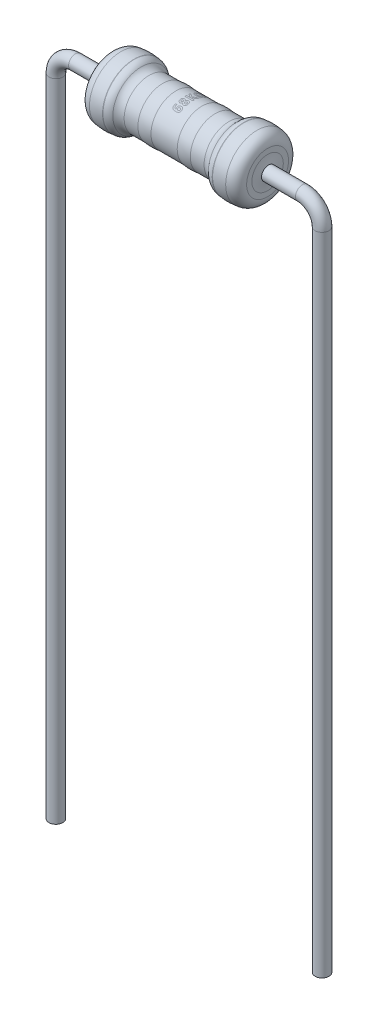
SolidWorks part; units mm, degrees
material "Plain Carbon Steel"
ref_plane "Front Plane" through (0, 0, 0) normal (0, 0, 1) x (1, 0, 0)
ref_plane "Top Plane" through (0, 0, 0) normal (0, 1, 0) x (1, 0, 0)
ref_plane "Right Plane" through (0, 0, 0) normal (1, 0, 0) x (0, 0, -1)
sketch "Sketch1" plane through (0, 0, 0) normal (0, 0, 1) x (1, 0, 0)
  line L0 (-4.33, 0) -> (4.33, 0)
  line L1 (-5.08, -0.75) -> (-5.08, -25.4)
  line L2 (5.08, -0.75) -> (5.08, -25.4)
  line L3 (-5.08, -25.4) -> (5.08, -25.4) construction
  line L4 (0, 0) -> (0, -25.4) construction
  arc A0 (-4.33, 0) -> (-5.08, -0.75) centre (-4.33, -0.75) ccw
  arc A1 (4.33, 0) -> (5.08, -0.75) centre (4.33, -0.75) cw
  dimension "D2" = 0.75
  dimension "D1" = 10.16
  dimension "D3" = 25.4
ref_plane "Plane1" through (-5.08, -25.4, 0) normal (0, -1, 0) x (-1, 0, 0)
sketch "Sketch2" plane through (-5.08, -25.4, 0) normal (0, -1, 0) x (-1, 0, 0)
  circle A0 centre (0, 0) radius 0.265
  dimension "D1" = 0.53
sweep "Sweep1" add profiles "Sketch2" path "Sketch1"
sketch "Sketch3" plane through (0, 0, 0) normal (0, 0, 1) x (1, 0, 0)
  line L0 (-3, 0) -> (3, 0)
  line L5 (-3, 0) -> (-3, 1.2)
  line L6 (3, 0) -> (3, 1.2)
  line L7 (-3, 1.2) -> (-1.75, 1.2)
  line L8 (3, 1.2) -> (1.75, 1.2)
  line L9 (-1.75, 1.2) -> (-1.75, 0.95)
  line L10 (-1.75, 0.95) -> (1.75, 0.95)
  line L11 (1.75, 0.95) -> (1.75, 1.2)
  line L12 (0, 0) -> (0, 0.95) construction
  dimension "D1" = 6
  dimension "D2" = 1.2
  dimension "D3" = 3.5
  dimension "D4" = 0.95
  dimension "D5" = 0.25
revolve "Revolve1" add sketch "Sketch3" angle 360 about L0
fillet "Fillet-1" radius 0.35 2 edges at (1.75, 0, 1.2) (-1.75, 0, 1.2)
fillet "Fillet-2" radius 0.4 4 edges at (3, 0, 1.2) (-3, 0, 1.2) (1.75, 0, 0.95) (-1.75, 0, 0.95)
sketch "Sketch5" plane through (0, 0, 0) normal (0, 0, 1) x (1, 0, 0)
  line L16 (-3, 0) -> (3, 0) construction
  line L17 (-2.6, 1.2) -> (-2.1, 1.2) construction
  line L18 (-2.6, 1.2) -> (-2.6, 0)
  line L19 (-2.6, 0) -> (-2.1, 0)
  line L20 (-2.1, 1.2) -> (-2.1, 0)
  line L21 (-1.75, 0.95) -> (1.75, 0.95) construction
  line L22 (2.6, 1.2) -> (2.1, 1.2) construction
  line L23 (2.6, 1.2) -> (2.6, 0)
  line L24 (2.6, 0) -> (2.1, 0)
  line L25 (2.1, 1.2) -> (2.1, 0)
  line L26 (-0.5, 0.95) -> (-1, 0.95) construction
  line L27 (-0.5, 0.95) -> (-0.5, 0)
  line L28 (-0.5, 0) -> (-1, 0)
  line L29 (-1, 0.95) -> (-1, 0)
  line L30 (-2.35, 1.2) -> (-2.35, 1.22) construction
  line L31 (1, 0.95) -> (0.5, 0.95) construction
  line L32 (1, 0.95) -> (1, 0)
  line L33 (1, 0) -> (0.5, 0)
  line L34 (0.5, 0.95) -> (0.5, 0)
  line L35 (-0.75, 0.95) -> (-0.75, 0.97) construction
  line L36 (0.75, 0.95) -> (0.75, 0.97) construction
  line L37 (2.35, 1.2) -> (2.35, 1.22) construction
  line L48 (-3, 0) -> (-3, 0.6)
  line L49 (-3, 0) -> (-3, 1.2) construction
  line L50 (-3, 0) -> (-3.05, 0)
  line L51 (-3.05, 0) -> (-3.05, 0.2)
  line L52 (3, 0) -> (3.05, 0)
  line L53 (3.05, 0) -> (3.05, 0.2)
  line L54 (3, 0) -> (3, 0.6)
  line L55 (3, 0) -> (3, 1.2) construction
  arc A0 (-2.6, 1.2) -> (-2.1, 1.2) centre (-2.35, -0.3525) cw
  arc A1 (-1, 0.95) -> (-0.5, 0.95) centre (-0.75, -0.6025) cw
  arc A2 (0.5, 0.95) -> (1, 0.95) centre (0.75, -0.6025) cw
  arc A3 (2.1, 1.2) -> (2.6, 1.2) centre (2.35, -0.3525) cw
  arc A6 (-3, 0.6) -> (-3.05, 0.2) centre (-4.625, 0.6) cw
  arc A7 (3.05, 0.2) -> (3, 0.6) centre (4.625, 0.6) cw
  dimension "D4" = 0.02
  dimension "D5" = 0.05
  dimension "D7" = 0.6
  dimension "D1" = 0.5
  dimension "D2" = 0.5
  dimension "D3" = 0.5
  dimension "D6" = 0.2
revolve "Revolve3" add sketch "Sketch5" angle 360 about L19
ref_plane "Plane2" through (0, 2, 0) normal (0, 1, 0) x (1, 0, 0)
sketch "Sketch6" plane through (0, 2, 0) normal (0, 1, 0) x (1, 0, 0)
  line L0 (0, 0) -> (0.15, 0) construction
  line L1 (0.15, 0.95) -> (0.15, -0.95) construction
  line L2 (0.5, 0.95) -> (-0.5, 0.95) construction
  text T0 "68KΩ" font "Calibri" height 0.3
  dimension "D1" = 0.15
wrap "Wrap1" sketch "Sketch6" wrap type scribe source sketch "Sketch6" face at (-0.5, -0.95, 0)
